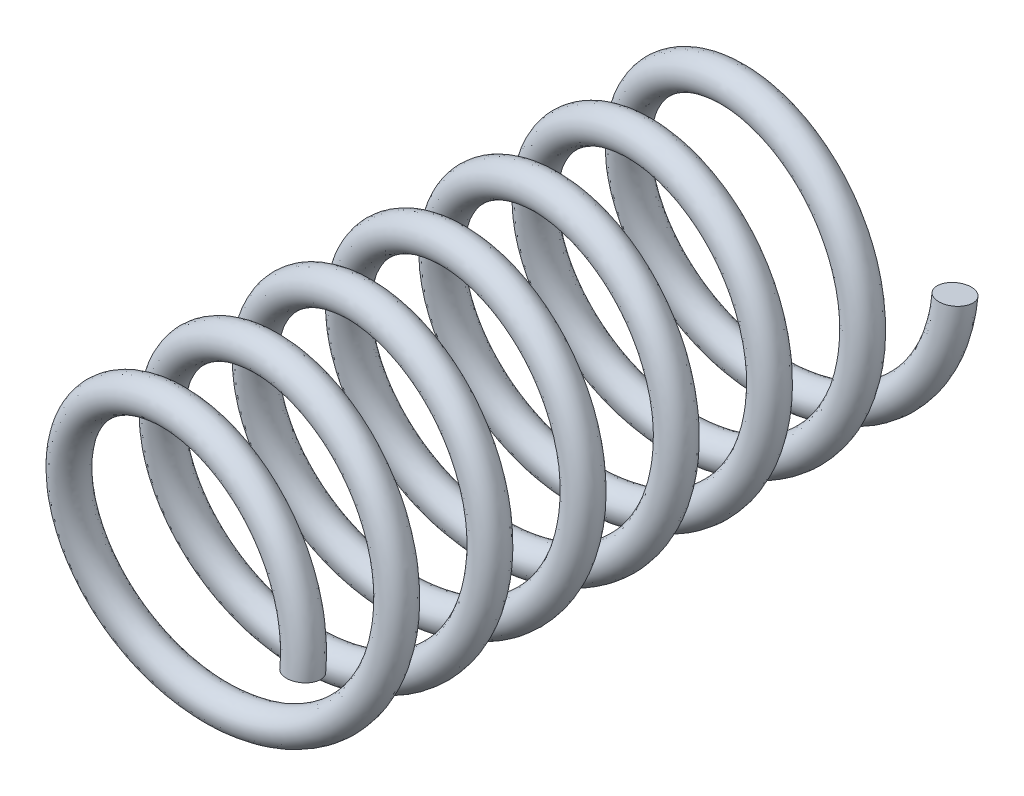
SolidWorks part; units mm, degrees
note: '?' marks a value the reader was unsure of.
ref_plane "Top" through (0, 0, 0) normal (0, 0, 1) x (1, 0, 0)
ref_plane "Right" through (0, 0, 0) normal (0, 1, 0) x (1, 0, 0)
ref_plane "Front" through (0, 0, 0) normal (1, 0, 0) x (0, 0, -1)
sketch "Sketch2" plane through (0, 0, 0) normal (0, 0, 1) x (1, 0, 0)
  circle A0 centre (0, 0) radius 19.05
  dimension "D1" = 38.1
curve "Helix/Spiral1" pitch 12.7 height 88.9 turns 7
sweep "Sweep1" add path "Helix/Spiral1" circular profile diameter 4.445 parameters "D3"=4.445
ref_axis "Axis1" through (0, 0, -80.9) along (0, 0, 1)?
sketch "Sketch3" plane through (0, 0, 0) normal (0, 0, 1) x (1, 0, 0)
  circle A0 centre (0, 0) radius 19.5
sketch "Sketch4" plane through (0, 0, 0) normal (0, 0.9944, -0.1055) x (1, 0, 0)
  circle A0 centre (19.05, 0) radius 2.2225
  point P2 (19.05, 2.2225)
sketch "Sketch5" plane through (0, -9.3276, 0.9897) normal (0, -0.9944, 0.1055) x (1, 0, 0)
  circle A0 centre (19.05, 88.4038) radius 2.2225
  point P2 (19.05, 90.6263)
